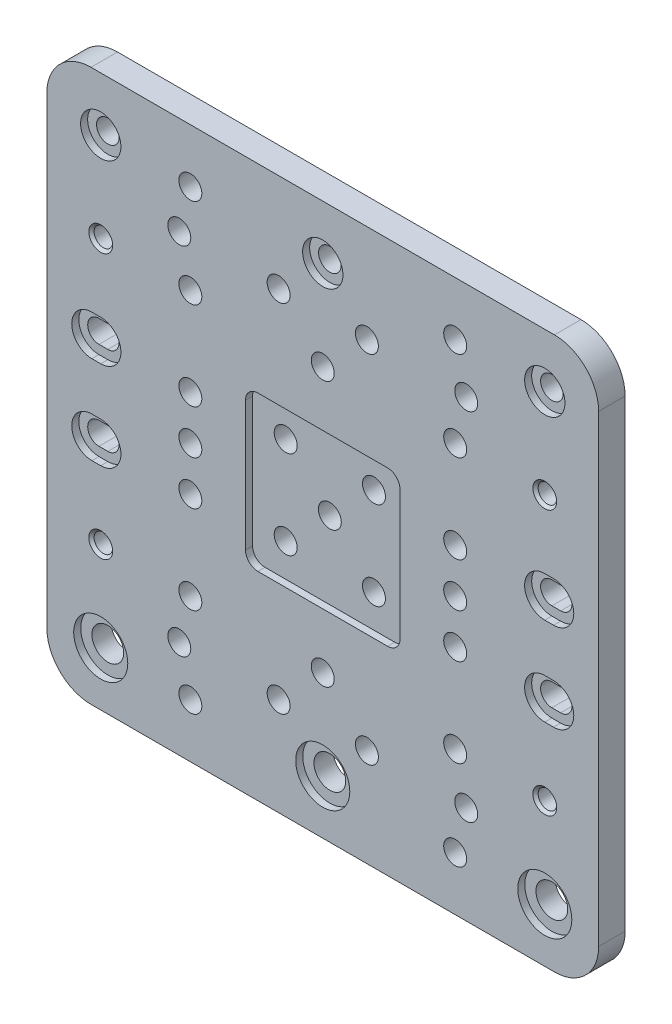
SolidWorks part; units mm, degrees
material "6061-T6 (SS)"
ref_plane "Front Plane" through (0, 0, 0) normal (0, 0, 1) x (1, 0, 0)
ref_plane "Top Plane" through (0, 0, 0) normal (0, 1, 0) x (1, 0, 0)
ref_plane "Right Plane" through (0, 0, 0) normal (1, 0, 0) x (0, 0, -1)
sketch "Sketch1" plane through (0, 0, 0) normal (0, 0, 1) x (1, 0, 0)
  line L1 (62.5, -62.5) -> (-62.5, -62.5)
  line L2 (62.5, -62.5) -> (62.5, 62.5)
  line L3 (62.5, 62.5) -> (-62.5, 62.5)
  line L4 (-62.5, -62.5) -> (-62.5, 62.5)
  line L5 (62.5, -62.5) -> (-62.5, 62.5) construction
  line L6 (62.5, 62.5) -> (-62.5, -62.5) construction
  point P0 (0, 0)
  dimension "D1" = 125
extrude "Boss-Extrude1" add sketch "Sketch1" along normal blind 6
hole_wizard "M5 Clearance Hole1" positions "Sketch3" profile "Sketch2" hole size "M5" standard "ANSI Metric" end condition through all
sketch "Sketch3" plane through (0, 0, 6) normal (0, 0, 1) x (1, 0, 0)
  line L0 (-62.5, 0) -> (0, 0) construction
  line L1 (-62.5, 62.5) -> (-62.5, -62.5) construction
  line L2 (0, 0) -> (0, 62.5) construction
  line L3 (62.5, 62.5) -> (-62.5, 62.5) construction
  point P0 (0, 0)
  point P3 (-10, 10)
  point P5 (-30, 30)
  point P7 (0, 30)
  point P20 (-30, 0)
  point P25 (-30, 10)
  point P29 (-30, -10)
  point P30 (0, -30)
  point P31 (-30, -30)
  point P32 (-10, -10)
  point P33 (10, -10)
  point P34 (30, -30)
  point P35 (30, -10)
  point P36 (30, 10)
  point P37 (30, 0)
  point P38 (30, 30)
  point P39 (10, 10)
  point P43 (-30, 50.3)
  point P45 (-32.5, 40.3)
  point P47 (-10, 40.3)
  point P53 (10, 40.3)
  point P54 (32.5, 40.3)
  point P55 (30, 50.3)
  point P56 (30, -50.3)
  point P57 (32.5, -40.3)
  point P58 (10, -40.3)
  point P59 (-10, -40.3)
  point P60 (-32.5, -40.3)
  point P61 (-30, -50.3)
  dimension "D1" = 60
  dimension "D2" = 60
  dimension "D3" = 20
  dimension "D4" = 20
  dimension "D5" = 65
  dimension "D6" = 100.6
  dimension "D7" = 80.6
sketch "Sketch2" plane through (0, 0, 6) normal (1, 0, 0) x (0, -1, 0)
  line L0 (0, 0) -> (0, 6)
  line L1 (0, 6) -> (2.6, 6)
  line L2 (2.6, 6) -> (2.6, 0)
  line L5 (2.6, 0) -> (0, 0)
  line L11 (0, -6.35) -> (0, 107.95) construction
  dimension "Thru Hole Dia." = 5.2
  dimension "Thru Hole Depth" = 6
sketch "Sketch4" plane through (0, 0, 6) normal (0, 0, 1) x (1, 0, 0)
  line L0 (-50.3, 10) -> (-52.3, 10) construction
  line L1 (-50.3, 7.45) -> (-52.3, 7.45)
  line L2 (-50.3, 12.55) -> (-52.3, 12.55)
  line L3 (-62.5, 0) -> (0, 0) construction
  line L4 (-62.5, 62.5) -> (-62.5, -62.5) construction
  line L5 (0, 0) -> (0, 62.5) construction
  line L6 (62.5, 62.5) -> (-62.5, 62.5) construction
  line L7 (-50.3, -10) -> (-52.3, -10) construction
  line L8 (-50.3, -7.45) -> (-52.3, -7.45)
  line L9 (-50.3, -12.55) -> (-52.3, -12.55)
  line L10 (50.3, 10) -> (52.3, 10) construction
  line L11 (50.3, 7.45) -> (52.3, 7.45)
  line L12 (50.3, 12.55) -> (52.3, 12.55)
  line L13 (50.3, -10) -> (52.3, -10) construction
  line L14 (50.3, -7.45) -> (52.3, -7.45)
  line L15 (50.3, -12.55) -> (52.3, -12.55)
  circle A0 centre (-50.3, 50.3) radius 2.55
  circle A1 centre (0, 50.3) radius 2.55
  circle A2 centre (-50.3, -50.3) radius 3.6
  arc A3 (-50.3, 7.45) -> (-50.3, 12.55) centre (-50.3, 10) ccw
  arc A4 (-52.3, 12.55) -> (-52.3, 7.45) centre (-52.3, 10) ccw
  circle A5 centre (50.3, 50.3) radius 2.55
  circle A6 centre (50.3, -50.3) radius 3.6
  circle A7 centre (0, -50.3) radius 3.6
  arc A8 (-50.3, -7.45) -> (-50.3, -12.55) centre (-50.3, -10) cw
  arc A9 (-52.3, -12.55) -> (-52.3, -7.45) centre (-52.3, -10) cw
  arc A10 (50.3, 7.45) -> (50.3, 12.55) centre (50.3, 10) cw
  arc A11 (52.3, 12.55) -> (52.3, 7.45) centre (52.3, 10) cw
  arc A12 (50.3, -7.45) -> (50.3, -12.55) centre (50.3, -10) ccw
  arc A13 (52.3, -12.55) -> (52.3, -7.45) centre (52.3, -10) ccw
  point P8 (-51.3, 10)
  point P29 (-51.3, -10)
  point P36 (51.3, 10)
  point P43 (51.3, -10)
  dimension "D1" = 7.2
  dimension "D2" = 5.1
  dimension "D3" = 100.6
  dimension "D4" = 100.6
  dimension "D5" = 50.3
  dimension "D6" = 5.1
  dimension "D7" = 2
  dimension "D8" = 20
extrude "Cut-Extrude1" cut sketch "Sketch4" against normal through all
sketch "Sketch5" plane through (0, 0, 6) normal (0, 0, 1) x (1, 0, 0)
  line L0 (-50.3, 10) -> (-52.3, 10) construction
  line L1 (17.5, -17.5) -> (-17.5, -17.5)
  line L2 (17.5, -17.5) -> (17.5, 17.5)
  line L3 (17.5, 17.5) -> (-17.5, 17.5)
  line L4 (-17.5, -17.5) -> (-17.5, 17.5)
  line L5 (17.5, -17.5) -> (-17.5, 17.5) construction
  line L6 (17.5, 17.5) -> (-17.5, -17.5) construction
  line L7 (-50.3, 5.432) -> (-52.3, 5.432)
  line L8 (-50.3, 14.568) -> (-52.3, 14.568)
  line L9 (-50.3, -10) -> (-52.3, -10) construction
  line L10 (-50.3, -14.568) -> (-52.3, -14.568)
  line L11 (-50.3, -5.432) -> (-52.3, -5.432)
  line L12 (50.3, 10) -> (52.3, 10) construction
  line L13 (50.3, 14.568) -> (52.3, 14.568)
  line L14 (50.3, 5.432) -> (52.3, 5.432)
  line L15 (50.3, -10) -> (52.3, -10) construction
  line L16 (50.3, -5.432) -> (52.3, -5.432)
  line L17 (50.3, -14.568) -> (52.3, -14.568)
  circle A0 centre (-50.3, 50.3) radius 4.5675
  circle A1 centre (0, 50.3) radius 4.5675
  circle A2 centre (50.3, 50.3) radius 4.5675
  circle A3 centre (-50.3, -50.3) radius 6.125
  circle A4 centre (0, -50.3) radius 6.125
  circle A5 centre (50.3, -50.3) radius 6.125
  arc A6 (-50.3, 5.432) -> (-50.3, 14.568) centre (-50.3, 10) ccw
  arc A7 (-52.3, 14.568) -> (-52.3, 5.432) centre (-52.3, 10) ccw
  arc A8 (-50.3, -14.568) -> (-50.3, -5.432) centre (-50.3, -10) ccw
  arc A9 (-52.3, -5.432) -> (-52.3, -14.568) centre (-52.3, -10) ccw
  arc A10 (50.3, 14.568) -> (50.3, 5.432) centre (50.3, 10) ccw
  arc A11 (52.3, 5.432) -> (52.3, 14.568) centre (52.3, 10) ccw
  arc A12 (50.3, -5.432) -> (50.3, -14.568) centre (50.3, -10) ccw
  arc A13 (52.3, -14.568) -> (52.3, -5.432) centre (52.3, -10) ccw
  point P0 (0, 0)
  point P26 (-51.3, 10)
  point P37 (-51.3, -10)
  point P42 (51.3, 10)
  point P51 (51.3, -10)
  dimension "D3" = 12.25
  dimension "D4" = 9.135
  dimension "D1" = 35
  dimension "D2" = 9.136
extrude "Cut-Extrude2" cut sketch "Sketch5" against normal blind 1.6
fillet "Fillet1" radius 10 4 edges at (-62.5, 62.5, 3) (62.5, 62.5, 3) (62.5, -62.5, 3) (-62.5, -62.5, 3)
fillet "Fillet2" radius 2.8 4 edges at (17.5, -17.5, 5.2) (-17.5, -17.5, 5.2) (17.5, 17.5, 5.2) (-17.5, 17.5, 5.2)
hole_wizard "M5x0.8 Tapped Hole1" positions "Sketch7" profile "Sketch6" tap size "M5x0.8" standard "ANSI Metric" end condition through all
sketch "Sketch7" plane through (0, 0, 6) normal (0, 0, 1) x (1, 0, 0)
  line L0 (-62.5, 0) -> (0, 0) construction
  line L1 (-62.5, 52.5) -> (-62.5, -52.5) construction
  line L2 (0, 0) -> (0, 62.5) construction
  line L3 (52.5, 62.5) -> (-52.5, 62.5) construction
  point P0 (-50.3, 30)
  point P15 (50.3, 30)
  point P17 (50.3, -30)
  point P18 (-50.3, -30)
  dimension "D1" = 60
  dimension "D2" = 100.6
sketch "Sketch6" plane through (-50.3, 30, 6) normal (1, 0, 0) x (0, -1, 0)
  line L0 (0, 0) -> (0, 6)
  line L1 (0, 6) -> (2.1, 6)
  line L2 (2.1, 6) -> (2.1, 0)
  line L5 (2.1, 0) -> (0, 0)
  line L11 (0, -6.35) -> (0, 107.95) construction
  dimension "Thru Tap Drill Dia." = 4.2
  dimension "Thru Tap Drill Depth" = 6
cosmetic thread "Hole Thread1" parameters "D2"=5
cosmetic thread "Hole Thread2" parameters "D2"=5
cosmetic thread "Hole Thread3" parameters "D2"=5
cosmetic thread "Hole Thread4" parameters "D2"=5
chamfer "Chamfer1" distance 0.6 angle 45 4 edges at (52.4, -30, 6) (52.4, 30, 6) (-48.2, 30, 6) (-48.2, -30, 6)
